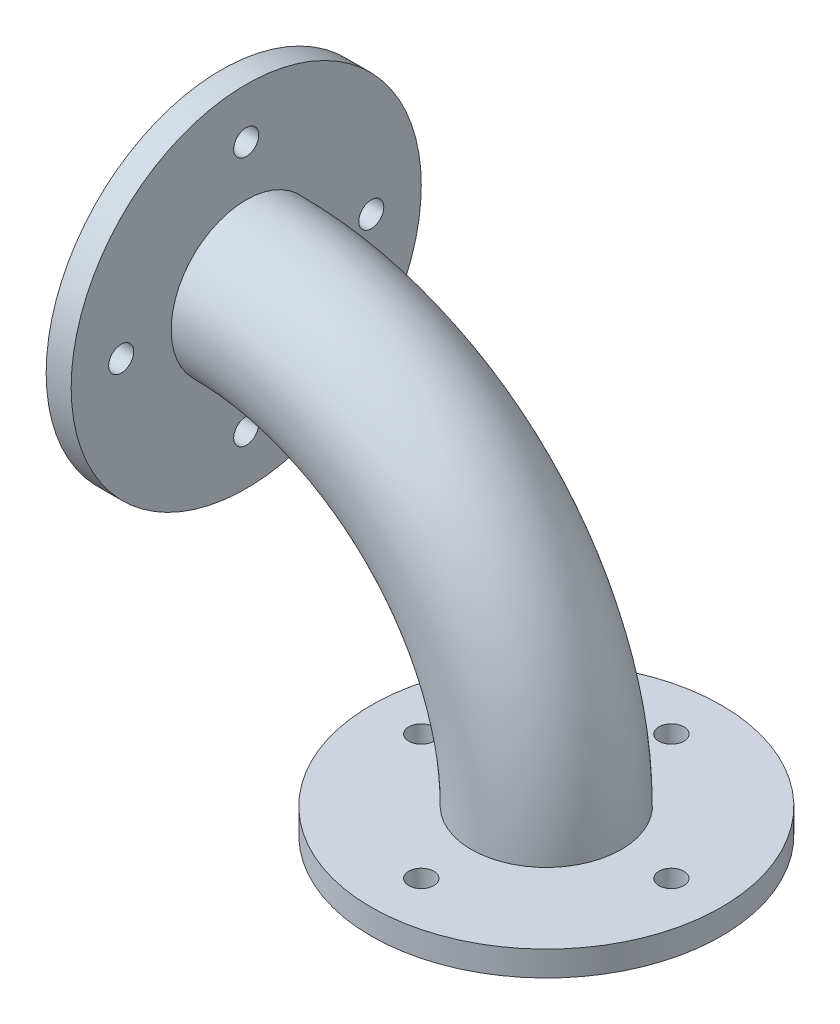
SolidWorks part; units mm, degrees
ref_plane "Front Plane" through (0, 0, 0) normal (0, 0, 1) x (1, 0, 0)
ref_plane "Top Plane" through (0, 0, 0) normal (0, 1, 0) x (1, 0, 0)
ref_plane "Right Plane" through (0, 0, 0) normal (1, 0, 0) x (0, 0, -1)
sketch "Sketch1" plane through (0, 0, 0) normal (0, 0, 1) x (1, 0, 0)
  arc A0 (76.2, 0) -> (-4.1019, 76.0895) centre (0, 0) ccw
  dimension "D1" = 76.2
sketch "Sketch3" plane through (0, 0, 0) normal (0, 1, 0) x (1, 0, 0)
  line L0 (-4.1019, 0) -> (76.2, 0) construction
  circle A0 centre (76.2, 0) radius 19.05
  circle A1 centre (76.2, 0) radius 12.7
  dimension "D1" = 25.4
  dimension "D2" = 38.1
  dimension "D3" = 76.2
sweep "Sweep1" add profiles "Sketch3" path "Sketch1"
sketch "Sketch4" plane through (0, 0, 0) normal (0, -1, 0) x (1, 0, 0)
  circle A0 centre (76.2, 0) radius 44.45
  circle A1 centre (76.2, 0) radius 31.75 construction
  circle A2 centre (76.2, 31.75) radius 3.175
  circle A3 centre (107.95, 0) radius 3.175
  circle A4 centre (76.2, 0) radius 31.75 construction
  circle A5 centre (76.2, -31.75) radius 3.175
  circle A6 centre (76.2, 0) radius 31.75 construction
  circle A7 centre (44.45, 0) radius 3.175
  circle A8 centre (76.2, 0) radius 31.75 construction
  point P18 (76.2, 0)
  dimension "D2" = 63.5
  dimension "D3" = 88.9
  dimension "D4" = 6.35
  dimension "D1" = 4
extrude "Boss-Extrude1" add sketch "Sketch4" along normal blind 6.35 contours A0 | A7 | A5 | A3 | A2
ref_axis "Axis2" through (0, 0, -48.895) along (0, 0, 1)
ref_plane "Plane1" through (0, 0, 0) normal (-0.7071, 0.7071, 0) x (0, 0, 1)
mirror "Mirror1" about plane through (0, 0, 0) normal (-0.7071, 0.7071, 0) of "Boss-Extrude1"
